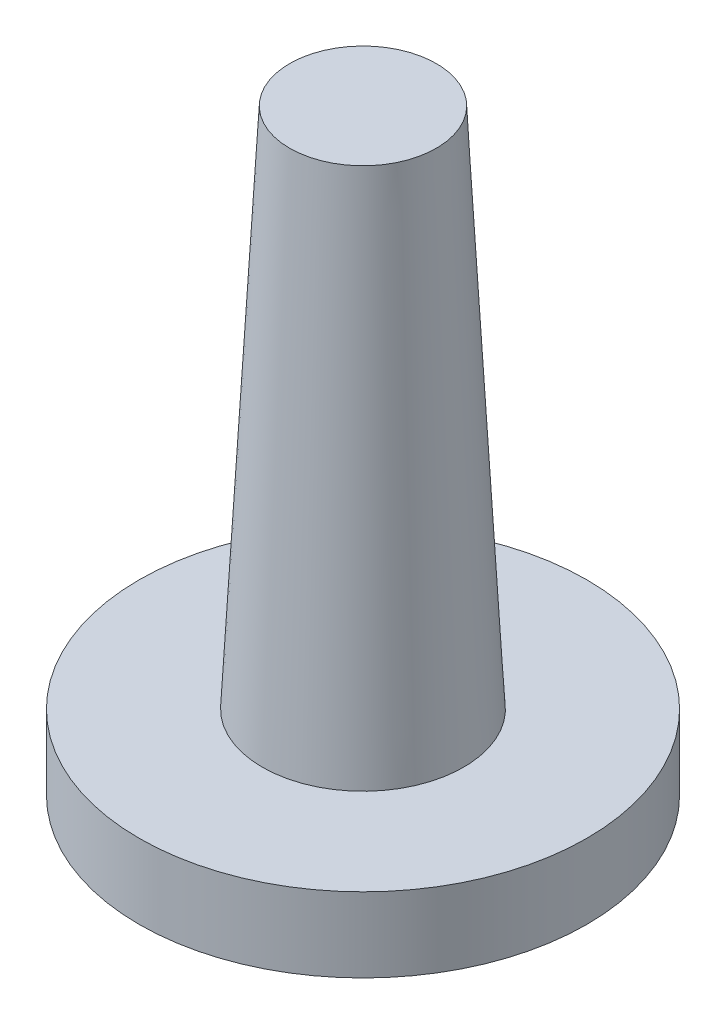
SolidWorks part; units mm, degrees
ref_plane "Plan de face" through (0, 0, 0) normal (0, 0, 1) x (1, 0, 0)
ref_plane "Plan de dessus" through (0, 0, 0) normal (0, 1, 0) x (1, 0, 0)
ref_plane "Plan de droite" through (0, 0, 0) normal (1, 0, 0) x (0, 0, -1)
sketch "Esquisse7" plane through (0, 0, 0) normal (0, 1, 0) x (1, 0, 0)
  circle A0 centre (0, 0) radius 3
  circle A1 centre (0, 0) radius 1.35
  dimension "D1" = 2.7
  dimension "D3" = 6
extrude "Boss.-Extru.5" add sketch "Esquisse7" along normal blind 7 draft 3 contours A1
extrude "Boss.-Extru.6" add sketch "Esquisse7<7>" against normal blind 1 contours A0
sketch "Esquisse7<7>" plane through (0, 0, 0) normal (0, 1, 0) x (1, 0, 0) same geometry as "Esquisse7"
